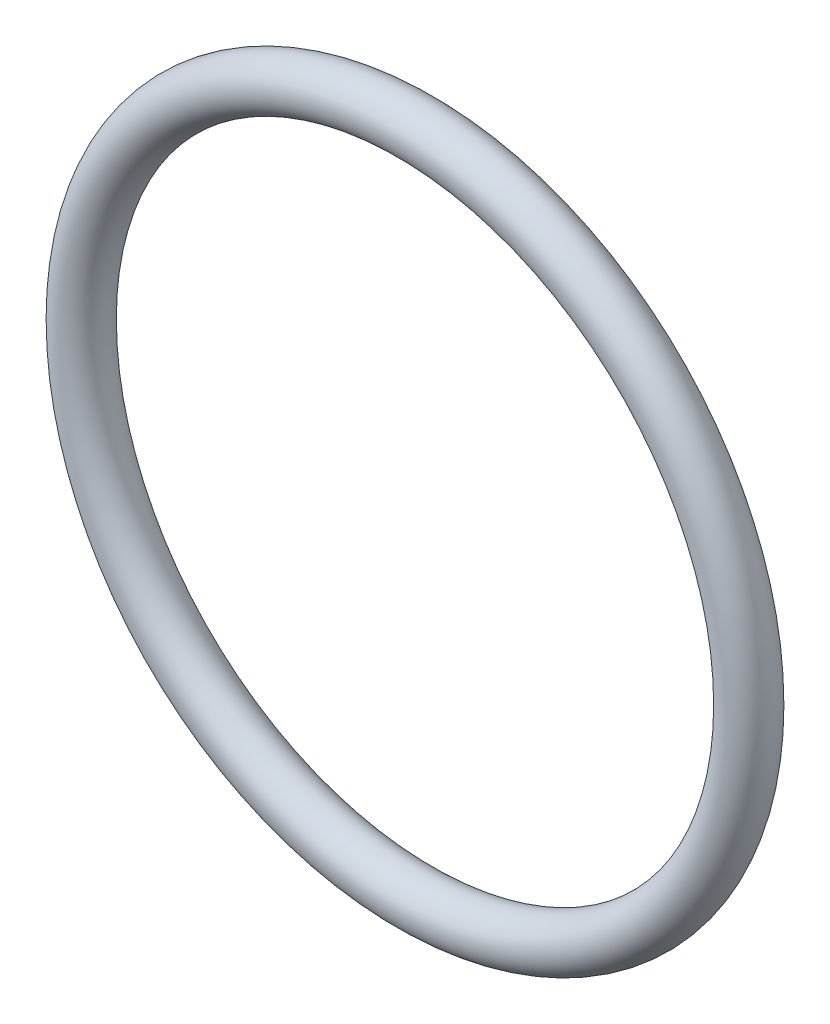
SolidWorks part; units mm, degrees
ref_plane "Front" through (0, 0, 0) normal (0, 0, 1) x (1, 0, 0)
ref_plane "Top" through (0, 0, 0) normal (0, 1, 0) x (1, 0, 0)
ref_plane "Right" through (0, 0, 0) normal (1, 0, 0) x (0, 0, -1)
ref_axis "Axis1" through (0, 0, -88.99) along (0, 0, 1)
sketch "Sketch1" plane through (0, 0, 0) normal (1, 0, 0) x (0, -1, 0)
  line L0 (0, -0.7435) -> (0, 0.7435) construction
  line L2 (-55, 0) -> (55, 0) construction
  line L3 (-9.243, 0) -> (9.243, 0) construction
  circle A0 centre (9.9865, 0) radius 0.7435
  point P9 (9.243, 0)
  point P10 (10.73, 0)
  point P13 (9.9865, 0.7435)
  point P14 (9.9865, -0.7435)
  dimension "Width" = 1.487
  dimension "ID" = 18.486
  dimension "OD" = 21.46
sketch "Sketch2" plane through (0, 0, 0) normal (1, 0, 0) x (0, 0, -1)
  line L0 (-0.7435, 0) -> (0.7435, 0) construction
  line L1 (-0.7435, 0) -> (0.7435, 0) construction
  circle A0 centre (0, -9.9865) radius 0.7435 construction
  circle A1 centre (0, -9.9865) radius 0.7435
revolve "Revolve1" add sketch "Sketch2" angle 360 about L1
